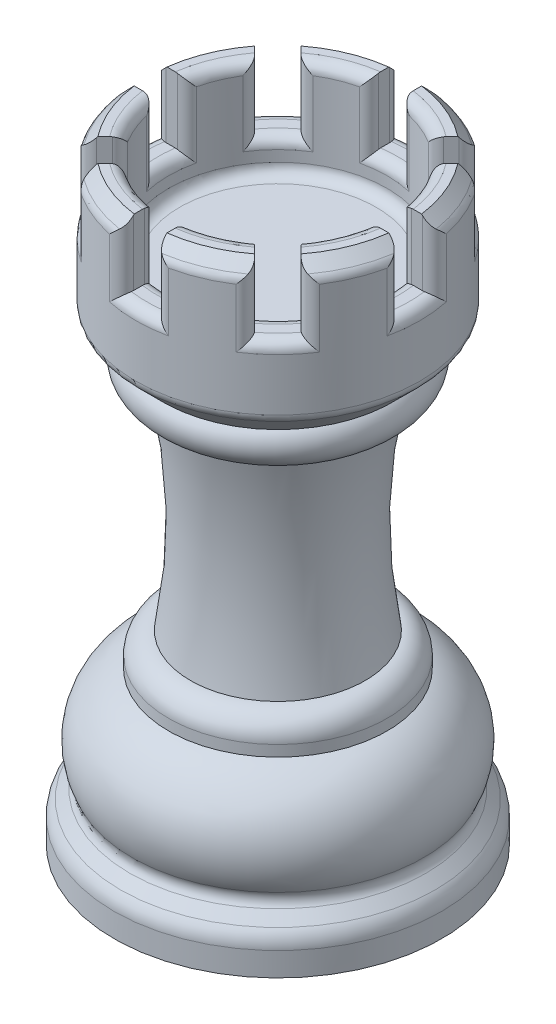
SolidWorks part; units mm, degrees
ref_plane "Front Plane" through (0, 0, 0) normal (0, 0, 1) x (1, 0, 0)
ref_plane "Top Plane" through (0, 0, 0) normal (0, 1, 0) x (1, 0, 0)
ref_plane "Right Plane" through (0, 0, 0) normal (1, 0, 0) x (0, 0, -1)
sketch "Sketch1" plane through (0, 0, 0) normal (0, 0, 1) x (1, 0, 0)
  line L0 (0, 65) -> (0, 10)
  line L1 (0, 10) -> (13, 10)
  line L2 (13, 15) -> (15, 13)
  line L3 (15, 13) -> (15, 10)
  line L4 (15, 10) -> (13, 10)
  line L5 (10, 23.97) -> (10, 24.97)
  line L6 (13, 52.79) -> (13, 63.79)
  line L7 (10.5, 50.29) -> (13, 52.79)
  line L8 (13, 63.79) -> (11.75, 65.04)
  line L9 (11.75, 65.04) -> (0, 65)
  arc A0 (10, 23.97) -> (13, 15) centre (8, 18.3144) cw
  arc A1 (8, 26.97) -> (10, 24.97) centre (8, 24.97) cw
  arc A2 (8.5, 46.97) -> (8, 26.97) centre (57.2239, 35.7457) ccw
  arc A3 (10.5, 50.29) -> (8.5, 46.97) centre (9.0765, 48.8851) cw
  dimension "D9" = 13
  dimension "D12" = 10.5
  dimension "D13" = 2
  dimension "D14" = 50
  dimension "D15" = 5.9988
  dimension "D16" = 2
  dimension "D1" = 55
  dimension "D2" = 3
  dimension "D3" = 2
  dimension "D4" = 8.97
  dimension "D5" = 3
  dimension "D6" = 20
  dimension "D7" = 3.32
  dimension "D8" = 8.5
  dimension "D10" = 8
  dimension "D11" = 10
  dimension "D17" = 2.5
  dimension "D19" = 12.25
revolve "Revolve1" add sketch "Sketch1" angle 360 about L0
sketch3d "3DSketch2"
  point P0 (0.0049, 70.0001, -0.0163)
sketch3d "3DSketch3"
  point P0 (0.0049, 70.0001, -0.0163)
ref_plane "Plane3" through (0, 70.0001, 0) normal (0, 1, 0) x (1, 0, 0)
sketch "Sketch8" plane through (0, 70.0001, 0) normal (0, 1, 0) x (1, 0, 0)
  circle A0 centre (0, 0) radius 10
extrude "Cut-Extrude2" cut sketch "Sketch8" against normal blind 9 and the other way blind 1 from offset 5 offset against normal yes
sketch "Sketch9" plane through (0, 70.0001, 0) normal (0, 1, 0) x (1, 0, 0)
  line L0 (15.4107, 13.2894) -> (3.6213, 1.5)
  line L1 (-13.1368, 13.1368) -> (-13.0465, 13.0465) construction
  line L5 (13.2894, 15.4107) -> (15.4107, 13.2894)
  line L6 (-13.6947, -15.816) -> (-15.816, -13.6947)
  line L7 (-15.816, -13.6947) -> (-3.6213, -1.5)
  line L8 (-14.1072, 11.9858) -> (-3.6213, 1.5)
  line L9 (-11.9858, 14.1072) -> (-14.1072, 11.9858)
  line L10 (13.2132, -15.3345) -> (15.3345, -13.2132)
  line L11 (15.3345, -13.2132) -> (3.6213, -1.5)
  line L13 (-16.6736, -1.5) -> (-16.6736, 1.5)
  line L14 (-16.6736, 1.5) -> (-3.6213, 1.5)
  line L15 (17.0804, 1.5) -> (17.0804, -1.5)
  line L16 (17.0804, -1.5) -> (3.6213, -1.5)
  line L18 (-1.5, 17.3097) -> (1.5, 17.3097)
  line L19 (1.5, 17.3097) -> (1.5, 3.6213)
  line L20 (1.5, -16.6717) -> (0, -16.6717)
  line L21 (0, -16.6717) -> (-1.5, -16.6717)
  line L22 (-1.5, -16.6717) -> (-1.5, -3.6213)
  line L23 (3.6213, 1.5) -> (17.0804, 1.5)
  line L25 (-1.5, 3.6213) -> (-1.5, 17.3097)
  line L26 (-1.5, 3.6213) -> (-11.9858, 14.1072)
  line L27 (1.5, 3.6213) -> (13.2894, 15.4107)
  line L30 (-3.6213, -1.5) -> (-16.6736, -1.5)
  line L32 (-1.5, -3.6213) -> (-13.6947, -15.816)
  line L33 (1.5, -3.6213) -> (1.5, -16.6717)
  line L34 (1.5, -3.6213) -> (13.2132, -15.3345)
extrude "Cut-Extrude3" cut sketch "Sketch9" against normal blind 6 and the other way blind 1 from offset 5 offset against normal yes
fillet "Fillet2" radius 1 1 edges at (-13, 52.79, 0)
fillet "Fillet3" radius 2 1 edges at (-15, 13, 0)
fillet "Fillet4" radius 1 1 edges at (-13, 15, 0)
fillet "Fillet5" radius 1 33 edges at (1.5, 62.0171, 9.8869) (0, 59.0001, 10) (-1.5, 62.0171, 9.8869) (-3.8268, 65.034, 9.2388) (-5.9304, 62.0171, 8.0517) (-7.0711, 59.0001, 7.0711) (-8.0517, 62.0171, 5.9304) (-9.2388, 65.034, 3.8268) (-9.8869, 62.0171, 1.5) (-10, 59.0001, 0) (-9.8869, 62.0171, -1.5) (-9.2388, 65.034, -3.8268) (-8.0517, 62.0171, -5.9304) (-7.0711, 59.0001, -7.0711) (-5.9304, 62.0171, -8.0517) (-3.8268, 65.034, -9.2388) (-1.5, 62.0171, -9.8869) (0, 59.0001, -10) (1.5, 62.0171, -9.8869) (3.8268, 65.034, -9.2388) (5.9304, 62.0171, -8.0517) (7.0711, 59.0001, -7.0711) (8.0517, 62.0171, -5.9304) (9.2388, 65.034, -3.8268) (9.8869, 62.0171, -1.5) (10, 59.0001, 0) (9.8869, 62.0171, 1.5) (9.2388, 65.034, 3.8268) (8.0517, 62.0171, 5.9304) (7.0711, 59.0001, 7.0711) (5.9304, 62.0171, 8.0517) (3.8268, 65.034, 9.2388) (0, 56.0001, 10)
fillet "Fillet8" radius 1 32 edges at (9.1924, 59.0001, 9.1924) (10.1917, 61.395, 8.0703) (12.0104, 63.79, 4.9749) (12.9132, 61.395, 1.5) (13, 59.0001, 0) (12.9132, 61.395, -1.5) (12.0104, 63.79, -4.9749) (10.1917, 61.395, -8.0703) (9.1924, 59.0001, -9.1924) (8.0703, 61.395, -10.1917) (4.9749, 63.79, -12.0104) (1.5, 61.395, -12.9132) (0, 59.0001, -13) (-1.5, 61.395, -12.9132) (-4.9749, 63.79, -12.0104) (-8.0703, 61.395, -10.1917) (-9.1924, 59.0001, -9.1924) (-10.1917, 61.395, -8.0703) (-12.0104, 63.79, -4.9749) (-12.9132, 61.395, -1.5) (-13, 59.0001, 0) (-12.9132, 61.395, 1.5) (-12.0104, 63.79, 4.9749) (-10.1917, 61.395, 8.0703) (-9.1924, 59.0001, 9.1924) (-8.0703, 61.395, 10.1917) (-4.9749, 63.79, 12.0104) (-1.5, 61.395, 12.9132) (0, 59.0001, 13) (1.5, 61.395, 12.9132) (4.9749, 63.79, 12.0104) (8.0703, 61.395, 10.1917)
